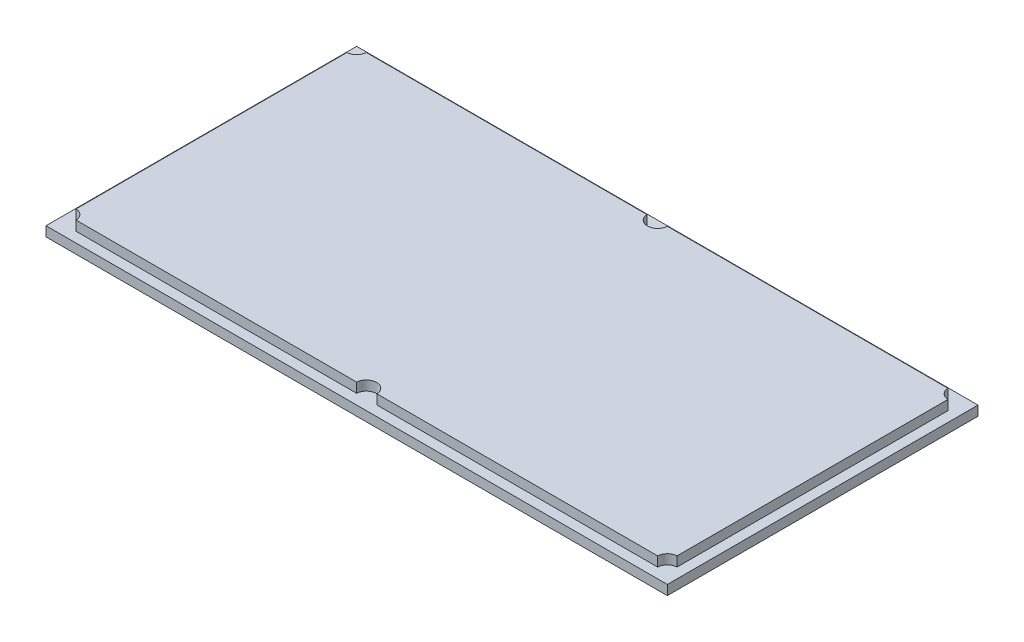
SolidWorks part; units mm, degrees
note: The reader was unsure of these and kept them because the rebuilt part matched: shared geometry of "Sketch3<7>".
ref_plane "Front Plane" through (0, 0, 0) normal (0, 0, 1) x (1, 0, 0)
ref_plane "Top Plane" through (0, 0, 0) normal (0, 1, 0) x (1, 0, 0)
ref_plane "Right Plane" through (0, 0, 0) normal (1, 0, 0) x (0, 0, -1)
sketch "Sketch3" plane through (0, 0, 0) normal (0, 1, 0) x (1, 0, 0)
  line L0 (64, 32) -> (-64, 32)
  line L3 (60, 30) -> (2, 30)
  line L4 (-62, -28) -> (-62, 28)
  line L5 (62, -30) -> (-62, 30) construction
  line L6 (62, 30) -> (-62, -30) construction
  line L7 (-64, -32) -> (-64, 32)
  line L8 (64, -32) -> (-64, -32)
  line L9 (64, -32) -> (64, 32)
  line L10 (0, 30) -> (0, -6) construction
  line L11 (-62, 0) -> (62, 0) construction
  line L12 (62, -28) -> (62, 28)
  line L13 (62, 30) -> (-62, 30) construction
  line L14 (-62, -30) -> (-62, 30) construction
  line L15 (62, -30) -> (62, 30) construction
  line L16 (62, -30) -> (-62, -30) construction
  line L18 (-2, 30) -> (-60, 30)
  line L19 (60, -30) -> (2, -30)
  line L20 (-2, -30) -> (-60, -30)
  line L21 (0, -32) -> (0, -52) construction
  line L22 (0, -52) -> (-27.8375, -52) construction
  line L23 (-62, -104) -> (62, -104) construction
  line L32 (0, -134) -> (0, -98) construction
  line L33 (62, -134) -> (-62, -74) construction
  line L34 (62, -74) -> (-62, -134) construction
  line L35 (-2, -74) -> (-60, -74)
  line L36 (60, -74) -> (2, -74)
  line L37 (-2, -134) -> (-60, -134)
  line L38 (62, -76) -> (62, -132)
  line L39 (64, -72) -> (64, -136)
  line L40 (64, -72) -> (-64, -72)
  line L41 (-64, -72) -> (-64, -136)
  line L42 (-62, -76) -> (-62, -132)
  line L43 (60, -134) -> (2, -134)
  line L44 (64, -136) -> (-64, -136)
  line L45 (-2.0976, -74.1) -> (-59.9024, -74.1)
  line L46 (59.9024, -74.1) -> (2.0976, -74.1)
  line L47 (61.9, -76.0976) -> (61.9, -131.9024)
  line L48 (59.9024, -133.9) -> (2.0976, -133.9)
  line L49 (-2.0976, -133.9) -> (-59.9024, -133.9)
  line L50 (-61.9, -76.0976) -> (-61.9, -131.9024)
  arc A0 (-62, 28) -> (-60, 30) centre (-62, 30) ccw
  arc A1 (62, 28) -> (60, 30) centre (62, 30) cw
  arc A2 (62, -28) -> (60, -30) centre (62, -30) ccw
  arc A3 (-62, -28) -> (-60, -30) centre (-62, -30) cw
  arc A8 (2, 30) -> (-2, 30) centre (0, 30) cw
  arc A9 (2, -30) -> (-2, -30) centre (0, -30) ccw
  arc A10 (2, -74) -> (-2, -74) centre (0, -74) cw
  arc A11 (2, -134) -> (-2, -134) centre (0, -134) ccw
  arc A12 (-62, -76) -> (-60, -74) centre (-62, -74) ccw
  arc A13 (62, -76) -> (60, -74) centre (62, -74) cw
  arc A14 (62, -132) -> (60, -134) centre (62, -134) ccw
  arc A15 (-62, -132) -> (-60, -134) centre (-62, -134) cw
  arc A16 (-61.9, -76.0976) -> (-59.9024, -74.1) centre (-62, -74) ccw
  arc A17 (2.0976, -74.1) -> (-2.0976, -74.1) centre (0, -74) cw
  arc A18 (61.9, -76.0976) -> (59.9024, -74.1) centre (62, -74) cw
  arc A19 (61.9, -131.9024) -> (59.9024, -133.9) centre (62, -134) ccw
  arc A20 (2.0976, -133.9) -> (-2.0976, -133.9) centre (0, -134) ccw
  arc A21 (-61.9, -131.9024) -> (-59.9024, -133.9) centre (-62, -134) cw
  point P0 (0, 0)
  point P52 (0, -104)
  dimension "D4" = 2
  dimension "D5" = 2
  dimension "D1" = 124
  dimension "D2" = 60
  dimension "D6" = 62
  dimension "D7" = 20
  dimension "D3" = 2
  dimension "D8" = 0.1
extrude "Boss-Extrude4" add sketch "Sketch3<7>" along normal blind 2 separate body contours L44 L39 L40 L41 A15 L42 A12 L35 A10 L36 A13 L38 A14 L43 A11 L37 | L42 A15 L37 A11 L43 A14 L38 A13 L36 A10 L35 A12 A21 L50 A16 L45 A17 L46 A18 L47 A19 L48 A20 L49 | L8 L7 L0 L9
sketch "Sketch3<7>" plane through (0, 0, 0) normal (0, 1, 0) x (1, 0, 0) same geometry as "Sketch3"
extrude "Boss-Extrude6" add sketch "Sketch3" along normal blind 4 contours L50 A21 L49 A20 L48 A19 L47 A18 L46 A17 L45 A16
